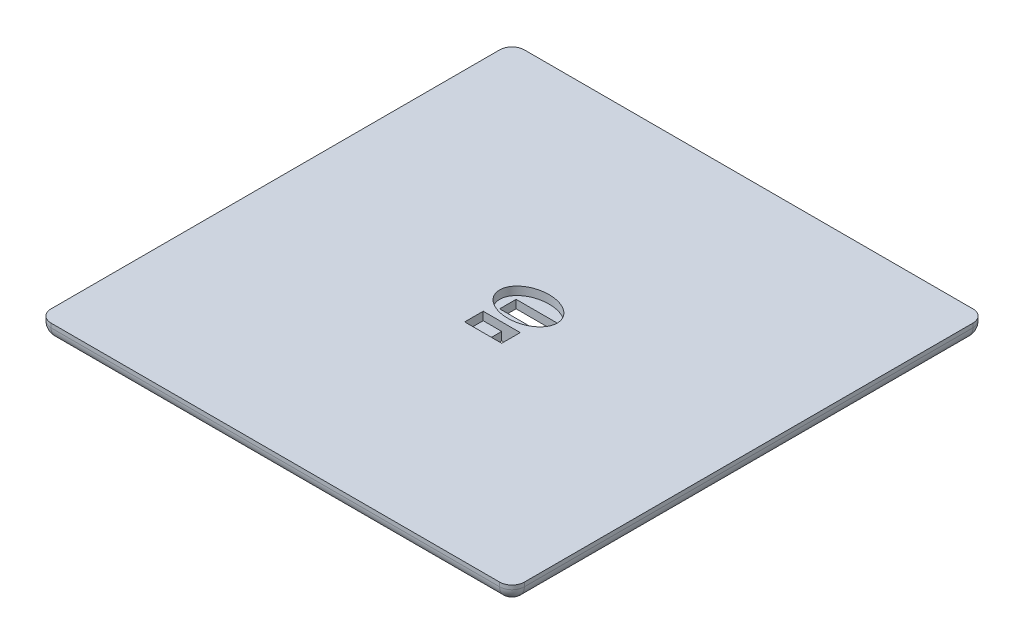
SolidWorks part; units mm, degrees
ref_plane "Front Plane" through (0, 0, 0) normal (0, 0, 1) x (1, 0, 0)
ref_plane "Top Plane" through (0, 0, 0) normal (0, 1, 0) x (1, 0, 0)
ref_plane "Right Plane" through (0, 0, 0) normal (1, 0, 0) x (0, 0, -1)
sketch "Sketch7" plane through (0, 0, 0) normal (0, 0, 1) x (1, 0, 0)
  line L0 (55, 0) -> (-55, 0) construction
  line L1 (-47.5, 4) -> (47.5, 4)
  line L2 (-47.5, 4) -> (-47.5, 0)
  line L3 (-47.5, 0) -> (47.5, 0)
  line L4 (47.5, 4) -> (47.5, 0)
extrude "Boss-Extrude4" add sketch "Sketch7" along normal blind 47.5 and the other way blind 47.5
sketch "Sketch8" plane through (0, 0, 0) normal (0, 0, 1) x (1, 0, 0)
  line L1 (-52.5, 4) -> (52.5, 4)
  line L2 (-52.5, 4) -> (-52.5, 8)
  line L3 (-52.5, 8) -> (52.5, 8)
  line L4 (52.5, 4) -> (52.5, 8)
extrude "Boss-Extrude5" add sketch "Sketch8" along normal blind 52.5 and the other way blind 52.5
sketch "Sketch9" plane through (0, 0, 0) normal (0, 0, 1) x (1, 0, 0)
  line L1 (-57.5, 12) -> (57.5, 12)
  line L2 (-57.5, 12) -> (-57.5, 8)
  line L3 (-57.5, 8) -> (57.5, 8)
  line L4 (57.5, 12) -> (57.5, 8)
extrude "Boss-Extrude6" add sketch "Sketch9" along normal blind 57.5 and the other way blind 57.5
sketch "Sketch10" plane through (0, 0, 0) normal (0, 1, 0) x (1, 0, 0)
  line L1 (-42.5, 42.5) -> (42.5, 42.5)
  line L2 (-42.5, 42.5) -> (-42.5, -42.5)
  line L3 (-42.5, -42.5) -> (42.5, -42.5)
  line L4 (42.5, 42.5) -> (42.5, -42.5)
extrude "Cut-Extrude1" cut sketch "Sketch10" against normal blind 3.5 and the other way blind 8
sketch "Sketch12" plane through (0, 12, 0) normal (0, 1, 0) x (1, 0, 0)
  ellipse E0 centre (0, 4) end of major axis (7, 4) minor radius 5
extrude "Cut-Extrude2" cut sketch "Sketch12" against normal blind 2
sketch "Sketch13" plane through (0, 0, 0) normal (0, 1, 0) x (1, 0, 0)
  line L1 (-5, 6) -> (5, 6)
  line L2 (-5, 6) -> (-5, 2)
  line L3 (-5, 2) -> (5, 2)
  line L4 (5, 6) -> (5, 2)
extrude "Cut-Extrude3" cut sketch "Sketch13" against normal through all and the other way blind 29
fillet "Fillet4" radius 3 24 edges at (-47.5, 2, -47.5) (-52.5, 6, -52.5) (-57.5, 10, -57.5) (-47.5, 0, 0) (-52.5, 4, 0) (-57.5, 8, 0) (-57.5, 10, 57.5) (-52.5, 6, 52.5) (-47.5, 2, 47.5) (0, 8, -57.5) (0, 4, -52.5) (0, 0, -47.5) (47.5, 2, -47.5) (52.5, 6, -52.5) (57.5, 10, -57.5) (57.5, 10, 57.5) (0, 8, 57.5) (57.5, 8, 0) (52.5, 4, 0) (0, 4, 52.5) (52.5, 6, 52.5) (47.5, 2, 47.5) (47.5, 0, 0) (0, 0, 47.5)
sketch "Sketch14" plane through (0, 12, 0) normal (0, 1, 0) x (1, 0, 0)
  line L1 (-4.5, -2.5) -> (4.5, -2.5)
  line L2 (-4.5, -2.5) -> (-4.5, -7)
  line L3 (-4.5, -7) -> (4.5, -7)
  line L4 (4.5, -2.5) -> (4.5, -7)
sketch "Sketch16" plane through (0, 12, 0) normal (0, 1, 0) x (1, 0, 0)
  line L1 (0, -2.5) -> (4.5, -2.5)
  line L2 (0, -2.5) -> (0, -7)
  line L3 (0, -7) -> (4.5, -7)
  line L4 (4.5, -2.5) -> (4.5, -7)
extrude "Cut-Extrude4" cut sketch "Sketch14" against normal blind 2
extrude "Cut-Extrude5" cut sketch "Sketch16" against normal blind 10
